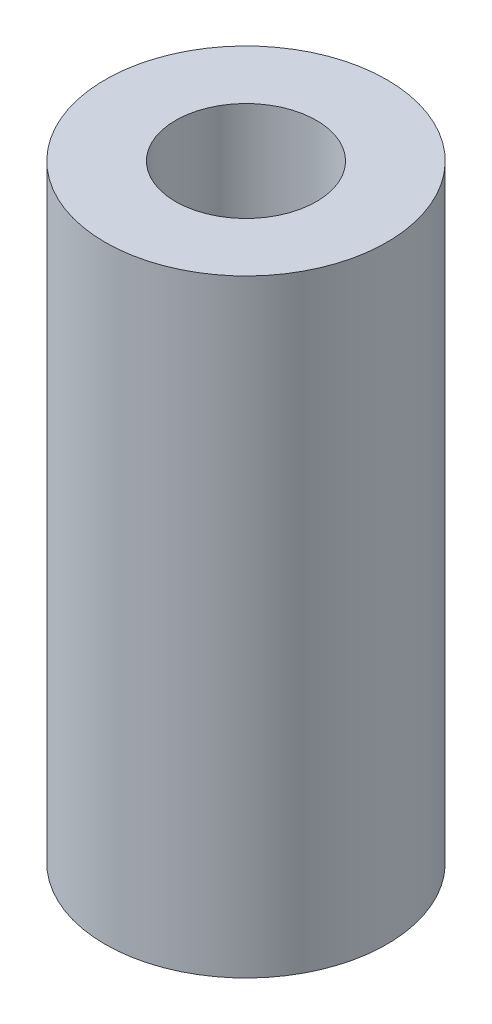
SolidWorks part; units mm, degrees
material "Delrin 2700 NC010, Low Viscosity Acetal Copolymer (SS)"
ref_plane "Front Plane" through (0, 0, 0) normal (0, 0, 1) x (1, 0, 0)
ref_plane "Top Plane" through (0, 0, 0) normal (0, 1, 0) x (1, 0, 0)
ref_plane "Right Plane" through (0, 0, 0) normal (1, 0, 0) x (0, 0, -1)
sketch "Sketch1" plane through (0, 0, 0) normal (0, 1, 0) x (1, 0, 0)
  circle A0 centre (0, 0) radius 1.5
  circle A1 centre (0, 0) radius 3
  point P2 (0, 0)
  dimension "D1" = 3
  dimension "D2" = 1.5
extrude "Boss-Extrude1" add sketch "Sketch1" along normal mid plane 12.948
